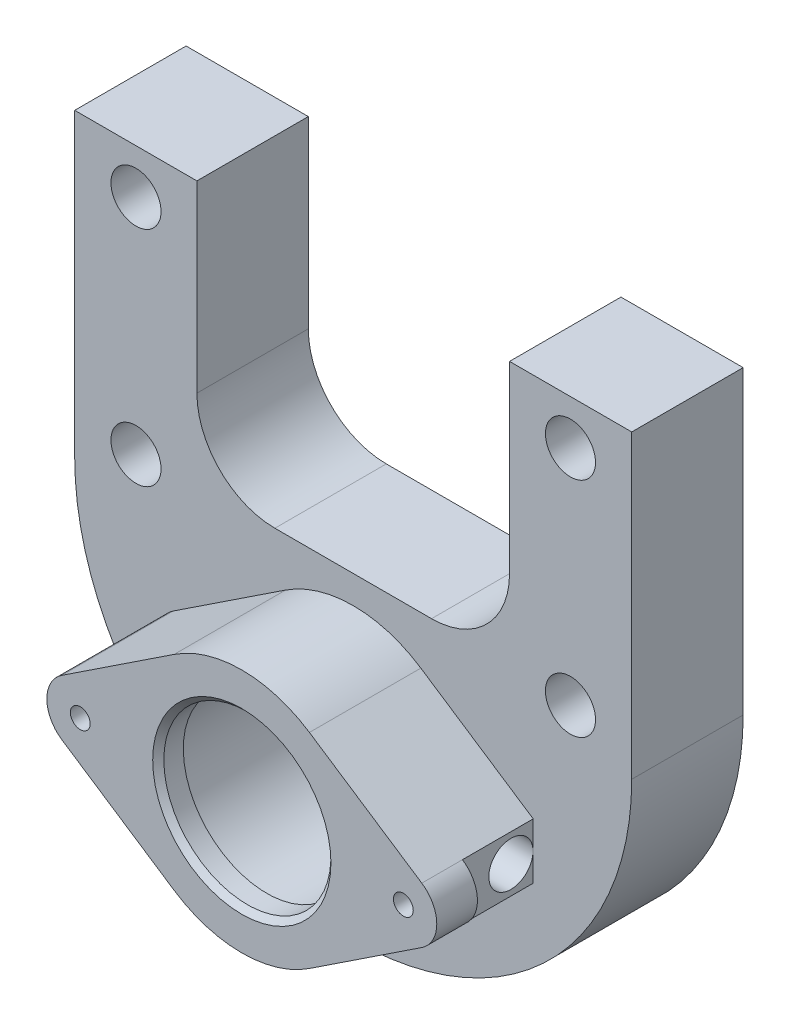
SolidWorks part; units mm, degrees
material "AISI 316 Annealed Stainless Steel Bar (SS)"
ref_plane "Front" through (0, 0, 0) normal (0, 0, 1) x (1, 0, 0)
ref_plane "Top" through (0, 0, 0) normal (0, 1, 0) x (1, 0, 0)
ref_plane "Right" through (0, 0, 0) normal (1, 0, 0) x (0, 0, -1)
sketch "Sketch1" plane through (0, 0, 0) normal (0, 0, 1) x (1, 0, 0)
  line L0 (0, 37) -> (0, 0) construction
  line L1 (-25, -15) -> (25, -15)
  line L2 (-25, -15) -> (-25, 37)
  line L3 (-25, 37) -> (25, 37)
  line L4 (25, -15) -> (25, 37)
  circle A0 centre (0, 0) radius 9.5 construction
  dimension "D3" = 19
  dimension "D5" = 15
  dimension "D1" = 52
  dimension "D2" = 50
extrude "Boss-Extrude1" add sketch "Sketch1" along normal blind 20
sketch "Sketch3" plane through (0, 0, 0) normal (1, 0, 0) x (0, 0, -1)
  line L0 (0, 0) -> (-20, 0)
  line L1 (-20, 0) -> (-20, 7.5)
  line L2 (-20, 7.5) -> (-17.75, 7.5)
  line L3 (-17.75, 7.5) -> (-17.75, 8)
  line L4 (-17.75, 8) -> (-7, 8)
  line L5 (-7, 8) -> (-7, 11)
  line L6 (-7, 11) -> (0, 11)
  line L7 (0, 37) -> (0, 0) construction
  line L8 (0, 11) -> (0, 0)
  line L9 (-20, -15) -> (-20, 37) construction
  dimension "D1" = 11
  dimension "D2" = 8
  dimension "D3" = 7.5
  dimension "D4" = 7
  dimension "D5" = 2.25
revolve "Cut-Revolve1" cut sketch "Sketch3" angle 360 about L0
hole_wizard "5/32 (0.15625) Diameter Hole1" positions "Sketch4" profile "Sketch5" hole size "5/32" standard "ANSI Inch" end condition up to next
sketch "Sketch4" plane through (25, 0, 0) normal (1, 0, 0) x (0, 0, -1)
  line L1 (0, 0) -> (-20, 0) construction
  line L2 (-20, -15) -> (-20, 37) construction
  point P0 (-12, 0)
  dimension "D1" = 8
sketch "Sketch5" plane through (25, 0, 12) normal (0, 1, 0) x (0, 0, -1)
  line L0 (0, 0) -> (0, 17)
  line L1 (0, 17) -> (1.9844, 17)
  line L2 (1.9844, 17) -> (1.9844, 0)
  line L5 (1.9844, 0) -> (0, 0)
  line L11 (0, -6.35) -> (0, 107.95) construction
  dimension "Thru Hole Dia." = 3.9688
  dimension "Thru Hole Depth" = 17
fillet "Fillet1" radius 5 1 edges at (0, 37, 20) profile chamfer
hole_wizard "#2-56 Tapped Hole1" positions "Sketch8" profile "Sketch9" tap size "#2-56" standard "ANSI Inch"
sketch "Sketch8" plane through (0, 0, 20) normal (0, 0, 1) x (1, 0, 0)
  line L0 (-14.5, 0) -> (14.5, 0)
  point P0 (-14.5, 0)
  point P2 (14.5, 0)
  dimension "D1" = 29
sketch "Sketch9" plane through (-14.5, 0, 20) normal (1, 0, 0) x (0, -1, 0)
  line L0 (0, 0) -> (0, 8.4542)
  line L1 (0, 8.4542) -> (0.889, 7.92)
  line L2 (0.889, 7.92) -> (0.889, 0)
  line L5 (0.889, 0) -> (0, 0)
  line L10 (0, 8.4542) -> (-0.889, 7.92) construction
  line L11 (0, -6.35) -> (0, 107.95) construction
  dimension "Tap Drill Dia." = 1.778
  dimension "Tap Drill Depth" = 7.92
  dimension "Drill Angle" = 118
cosmetic thread "Hole Thread1" parameters "D1"=6.2259, "D2"=2.1844
cosmetic thread "Hole Thread2" parameters "D1"=6.555, "D2"=2.1844
sketch "Sketch27" plane through (0, 0, 20) normal (0, 0, 1) x (1, 0, 0)
  line L0 (-16.1552, 2.5021) -> (-6.069, 9.1743)
  line L1 (6.069, 9.1743) -> (16.1552, 2.5021)
  line L2 (16.1552, -2.5021) -> (6.069, -9.1743)
  line L3 (-6.069, -9.1743) -> (-16.1552, -2.5021)
  arc A0 (-6.069, -9.1743) -> (6.069, -9.1743) centre (0, 0) ccw
  arc A1 (-16.1552, 2.5021) -> (-16.1552, -2.5021) centre (-14.5, 0) ccw
  arc A2 (16.1552, -2.5021) -> (16.1552, 2.5021) centre (14.5, 0) ccw
  arc A3 (6.069, 9.1743) -> (-6.069, 9.1743) centre (0, 0) ccw
  dimension "D1" = 11
  dimension "D2" = 3
extrude "Cut-Extrude6" cut sketch "Sketch27" against normal blind 10 flip side to cut
ref_plane "Plane1" through (17.5, 0, 0) normal (1, 0, 0) x (0, 0, -1)
hole_wizard "#8 Clearance Hole1" positions "Sketch20" profile "Sketch21" hole size "#8" standard "ANSI Inch" end condition through all
sketch "Sketch20" plane through (0, 0, 10) normal (0, 0, 1) x (1, 0, 0)
  line L0 (-19.5, 37) -> (-19.5, 33) construction
  line L1 (25, 37) -> (-25, 37) construction
  line L2 (-19.5, 33) -> (19.5, 33) construction
  line L3 (19.5, 33) -> (19.5, 37) construction
  line L6 (0, 33) -> (0, 37) construction
  line L9 (-19.5, 33) -> (-19.5, 13) construction
  line L10 (-19.5, 13) -> (19.5, 13) construction
  line L11 (19.5, 13) -> (19.5, 33) construction
  point P0 (19.5, 33)
  point P5 (-19.5, 33)
  point P36 (-19.5, 13)
  point P39 (19.5, 13)
  dimension "D1" = 39
  dimension "D2" = 4
  dimension "D3" = 20
sketch "Sketch21" plane through (19.5, 33, 10) normal (1, 0, 0) x (0, -1, 0)
  line L0 (0, 0) -> (0, 10)
  line L1 (0, 10) -> (2.2479, 10)
  line L2 (2.2479, 10) -> (2.2479, 0)
  line L5 (2.2479, 0) -> (0, 0)
  line L11 (0, -6.35) -> (0, 107.95) construction
  dimension "Thru Hole Dia." = 4.4958
  dimension "Thru Hole Depth" = 10
hole_wizard "1/8 (0.1250) Dowel Hole1" positions "Sketch10" profile "Sketch11" hole size "1/8" standard "ANSI Inch"
sketch "Sketch10" plane through (0, 0, 0) normal (0, 0, -1) x (-1, 0, 0)
  line L11 (-19.5, 13) -> (-19.5, 33) construction
  point P0 (-19.5, 23)
  point P28 (0, 0)
sketch "Sketch11" plane through (19.5, 23, 0) normal (1, 0, 0) x (0, 1, 0)
  line L0 (0, 0) -> (0, 5.9539)
  line L1 (0, 5.9539) -> (1.5875, 5)
  line L2 (1.5875, 5) -> (1.5875, 0)
  line L5 (1.5875, 0) -> (0, 0)
  line L10 (0, 5.9539) -> (-1.5875, 5) construction
  line L11 (0, -6.35) -> (0, 107.95) construction
  dimension "Hole Dia." = 3.175
  dimension "Hole Depth" = 5
  dimension "Drill Angle" = 118
hole_wizard "1/8 (0.1250) Dowel Slot1" positions "Sketch12" profile "Sketch13" size "1/8" standard "ANSI Inch" slot yes
sketch "Sketch12" plane through (0, 0, 0) normal (0, 0, -1) x (-1, 0, 0)
  line L0 (17.5, 23) -> (21.5, 23) construction
  line L6 (19.5, 33) -> (19.5, 13) construction
  point P0 (19.5, 23)
  point P22 (21.6317, 20.973)
  dimension "D1" = 4
sketch "Sketch13" plane through (-19.5, 23, 0) normal (1, 0, 0) x (0, 1, 0)
  line L0 (0, 0) -> (0, 5.9539)
  line L1 (0, 5.9539) -> (1.5875, 5)
  line L2 (1.5875, 5) -> (1.5875, 0)
  line L5 (1.5875, 0) -> (0, 0)
  line L10 (0, 5.9539) -> (-1.5875, 5) construction
  line L11 (0, -6.35) -> (0, 107.95) construction
  dimension "Hole Dia." = 3.175
  dimension "Hole Depth" = 5
  dimension "Drill Angle" = 118
sketch "Sketch22" plane through (0, 0, 0) normal (0, 0, -1) x (-1, 0, 0)
  circle A0 centre (0, 0) radius 10
  dimension "D1" = 20
chamfer "Chamfer1" distance 0.5 angle 45 2 edges at (0, 11, 0) (0, 7.5, 20)
sketch "Sketch24" plane through (0, 0, 20) normal (0, 0, 1) x (1, 0, 0)
  line L1 (-14.0313, 37) -> (14.0313, 37)
  line L2 (-14.0313, 37) -> (-14.0313, 20.5)
  line L3 (-7.0313, 13.5) -> (7.0313, 13.5)
  line L4 (14.0313, 37) -> (14.0313, 20.5)
  line L5 (0, 13.5) -> (0, 0) construction
  line L6 (25, 37) -> (-25, 37) construction
  arc A1 (7.0313, 13.5) -> (14.0313, 20.5) centre (7.0313, 20.5) ccw
  arc A2 (-14.0313, 20.5) -> (-7.0313, 13.5) centre (-7.0313, 20.5) ccw
  circle A3 centre (-19.5, 33) radius 2.2479 construction
  circle A4 centre (0, 0) radius 11.5 construction
  dimension "D2" = 7
  dimension "D4" = 3.2208
  dimension "D3" = 2
extrude "Cut-Extrude5" cut sketch "Sketch24" against normal through all
fillet "Fillet3" radius 25 2 edges at (25, -15, 5) (-25, -15, 5)
sketch "Sketch28" plane through (17.5, 0, 0) normal (1, 0, 0) x (0, 0, -1)
  line L1 (-10, 2.5021) -> (-16.35, 2.5021)
  line L2 (-10, 2.5021) -> (-10, -2.5021)
  line L3 (-10, -2.5021) -> (-16.35, -2.5021)
  line L4 (-16.35, 2.5021) -> (-16.35, -2.5021)
  line L5 (-20, 0) -> (-16.35, 0) construction
  line L6 (-20, 2.5021) -> (-20, -2.5021) construction
  line L7 (-10, 2.5021) -> (-20, 2.5021) construction
  line L8 (-10, -2.5021) -> (-20, -2.5021) construction
  line L9 (-10, 10) -> (-10, 37) construction
  dimension "D1" = 6.35
extrude "Cut-Extrude7" cut sketch "Sketch28" against normal up to vertex (1.3448 mm away) up to point (16.1552, 2.5021, 20)
